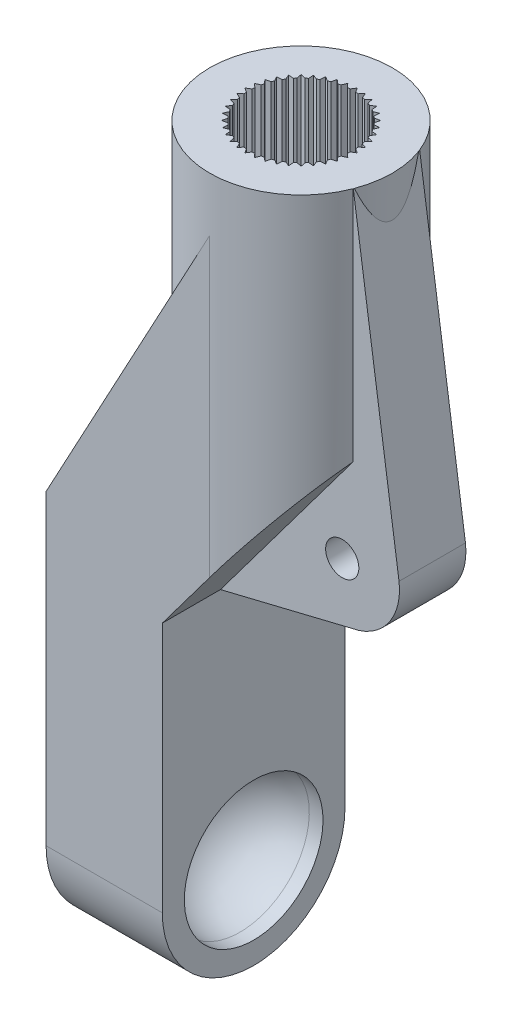
SolidWorks part; units mm, degrees
ref_plane "Front Plane" through (0, 0, 0) normal (0, 0, 1) x (1, 0, 0)
ref_plane "Top Plane" through (0, 0, 0) normal (0, 1, 0) x (1, 0, 0)
ref_plane "Right Plane" through (0, 0, 0) normal (1, 0, 0) x (0, 0, -1)
sketch "Sketch1" plane through (0, 0, 0) normal (0, 0, 1) x (1, 0, 0)
  line L0 (-0.147, 37.772) -> (-0.147, 24.3244)
  line L5 (2.4991, 12.8811) -> (10.853, 24.0251)
  line L6 (-4.501, 16.2484) -> (-0.147, 24.3244)
  line L7 (-0.147, 37.772) -> (10.853, 37.772)
  line L8 (10.853, 24.0251) -> (10.853, 37.772)
  line L9 (2.499, -7.728) -> (-4.501, -7.728)
  line L10 (10.853, 37.772) -> (13.4659, 16.992)
  line L11 (11.4819, 14.7528) -> (3.9024, 14.7528)
  line L12 (-4.501, -3.0008) -> (-4.501, 10.9802) construction
  line L14 (-7.001, 11.6112) -> (-0.147, 24.3244) construction
  line L15 (2.499, -8.0008) -> (2.4991, 8.7131) construction
  line L17 (-0.001, -5.5008) -> (-7.001, -5.5008) construction
  line L18 (-0.0009, 9.5461) -> (10.853, 24.0251) construction
  line L19 (-0.001, -5.5008) -> (-0.0009, 9.5461) construction
  line L35 (-4.501, -7.728) -> (-4.501, 16.2484)
  line L36 (2.499, -7.728) -> (2.4991, 12.8811)
  line L39 (2.499, -8.0008) -> (-9.501, -8.0008) construction
  line L40 (-9.501, -8.0008) -> (-9.501, 12.2422) construction
  line L41 (-9.501, 12.2422) -> (-2.647, 24.9553) construction
  line L42 (-2.647, 40.272) -> (-2.647, 24.9553) construction
  line L43 (-2.647, 40.272) -> (13.353, 40.272) construction
  line L44 (13.353, 23.1921) -> (13.353, 40.272) construction
  line L45 (2.4991, 8.7131) -> (13.353, 23.1921) construction
  line L47 (-2.501, -3.0008) -> (-4.501, -3.0008) construction
  line L48 (-2.501, -3.0008) -> (-2.5009, 10.3791) construction
  line L49 (-4.501, 10.9802) -> (2.353, 23.6934) construction
  line L50 (-2.5009, 10.3791) -> (8.353, 24.8581) construction
  line L51 (2.353, 35.272) -> (2.353, 23.6934) construction
  line L52 (2.353, 35.272) -> (8.353, 35.272) construction
  line L53 (8.353, 24.8581) -> (8.353, 35.272) construction
  line L54 (-7.001, -5.5008) -> (-7.001, 11.6112) construction
  circle A1 centre (9.8324, 18.1659) radius 1
  arc A2 (11.4819, 14.7528) -> (13.4659, 16.992) centre (11.4803, 16.7528) ccw
  point P2 (5.353, -2.228)
  point P4 (-7.6871, -2.228)
  point P20 (-7.001, -7.5008)
  point P21 (-7.001, 15.8257)
  dimension "D1" = 11
  dimension "D2" = 2.5
  dimension "D3" = 20.78
  dimension "D6" = 2.5
extrude "Boss-Extrude4" add sketch "Sketch1" along normal blind 11 contours L5 L8 L7 L0 L6 region at (2.1882, 17.5356, 0)
fillet "Fillet3" radius 5.5 2 edges at (-1.001, -7.728, 0) (-1.001, -7.728, 11)
sketch "Sketch4" plane through (0, 37.772, 0) normal (0, 1, 0) x (1, 0, 0)
  line L0 (-0.147, -5.5) -> (10.853, -5.5) construction
  line L1 (-0.147, -11) -> (-0.147, 0) construction
  line L2 (10.853, -11) -> (10.853, 0) construction
  line L3 (-0.147, 0) -> (-0.147, -11)
  line L4 (-0.147, -11) -> (10.853, -11)
  line L5 (10.853, -11) -> (10.853, 0)
  line L6 (10.853, 0) -> (-0.147, 0)
  circle A0 centre (5.353, -5.5) radius 5.5
  line M2 (-0.147, 0) -> (-0.147, -11)
  line M3 (-0.147, -11) -> (10.853, -11)
extrude "Cut-Extrude3" cut sketch "Sketch4" against normal up to surface (13.4477 mm away) contours A0 L6 M2 | A0 L3 M3 region at (1.0815, 37.772, 1.2285) region at (1.0815, 37.772, 9.7715) up to face at (-2.324, 20.2864, 5.5)
sketch "Sketch7" plane through (0, 37.772, 0) normal (0, 1, 0) x (1, 0, 0)
  line L0 (10.853, 0) -> (10.853, -11)
  line L1 (10.853, -11) -> (5.353, -11)
  line L2 (5.353, 0) -> (10.853, 0)
  circle A0 centre (5.353, -5.5) radius 5.5
  line M2 (5.353, -11) -> (10.853, -11)
  line M3 (10.853, -11) -> (10.853, 0)
  line M4 (10.853, 0) -> (5.353, 0)
extrude "Cut-Extrude9" cut sketch "Sketch7" against normal through all contours A0 L0 M4 | A0 M2 M3 region at (9.6244, 37.772, 1.2285) region at (9.6244, 37.772, 9.7715)
sketch3d "3DSketch1" plane through (0, 0, 0) normal (0, 0, 1) x (1, 0, 0)
ref_plane "Plane4" through (0, 0, 5.5) normal (0, 0, -1) x (-1, 0, 0)
sketch "Sketch8" plane through (0, 37.772, 0) normal (0, 1, 0) x (1, 0, 0)
  line L0 (5.353, -5.5) -> (10.853, -5.5) construction
  line L1 (8.7409, -5.5) -> (8.4736, -5.3352)
  line L2 (8.7409, -5.5) -> (8.4736, -5.6648)
  line L3 (8.6991, -6.03) -> (8.461, -5.8254)
  line L4 (8.6991, -6.03) -> (8.4094, -6.151)
  line L5 (8.575, -6.5469) -> (8.3718, -6.3076)
  line L6 (8.575, -6.5469) -> (8.2699, -6.6211)
  line L7 (8.3716, -7.0381) -> (8.2083, -6.7699)
  line L8 (8.3716, -7.0381) -> (8.0586, -7.0636)
  line L9 (8.0938, -7.4914) -> (7.9745, -7.2009)
  line L10 (8.0938, -7.4914) -> (7.7807, -7.4676)
  line L11 (7.7486, -7.8956) -> (7.6761, -7.5901)
  line L12 (7.7486, -7.8956) -> (7.443, -7.8232)
  line L13 (7.3443, -8.2409) -> (7.3206, -7.9278)
  line L14 (7.3443, -8.2409) -> (7.0539, -8.1216)
  line L15 (6.891, -8.5186) -> (6.9166, -8.2057)
  line L16 (6.891, -8.5186) -> (6.6228, -8.3554)
  line L17 (6.3999, -8.7221) -> (6.4741, -8.417)
  line L18 (6.3999, -8.7221) -> (6.1605, -8.5189)
  line L19 (5.8829, -8.8462) -> (6.0039, -8.5564)
  line L20 (5.8829, -8.8462) -> (5.6783, -8.608)
  line L21 (5.353, -8.8879) -> (5.5178, -8.6206)
  line L22 (5.353, -8.8879) -> (5.1881, -8.6206)
  line L23 (4.823, -8.8462) -> (5.0276, -8.608)
  line L24 (4.823, -8.8462) -> (4.702, -8.5564)
  line L25 (4.306, -8.7221) -> (4.5454, -8.5189)
  line L26 (4.306, -8.7221) -> (4.2318, -8.417)
  line L27 (3.8149, -8.5186) -> (4.0831, -8.3554)
  line L28 (3.8149, -8.5186) -> (3.7893, -8.2057)
  line L29 (3.3616, -8.2409) -> (3.652, -8.1216)
  line L30 (3.3616, -8.2409) -> (3.3853, -7.9278)
  line L31 (2.9573, -7.8956) -> (3.2629, -7.8232)
  line L32 (2.9573, -7.8956) -> (3.0298, -7.5901)
  line L33 (2.6121, -7.4914) -> (2.9252, -7.4676)
  line L34 (2.6121, -7.4914) -> (2.7314, -7.2009)
  line L35 (2.3343, -7.0381) -> (2.6473, -7.0636)
  line L36 (2.3343, -7.0381) -> (2.4976, -6.7699)
  line L37 (2.1309, -6.5469) -> (2.436, -6.6211)
  line L38 (2.1309, -6.5469) -> (2.3341, -6.3076)
  line L39 (2.0068, -6.03) -> (2.2965, -6.151)
  line L40 (2.0068, -6.03) -> (2.2449, -5.8254)
  line L41 (1.965, -5.5) -> (2.2323, -5.6648)
  line L42 (1.965, -5.5) -> (2.2323, -5.3352)
  line L43 (2.0068, -4.97) -> (2.2449, -5.1746)
  line L44 (2.0068, -4.97) -> (2.2965, -4.849)
  line L45 (2.1309, -4.4531) -> (2.3341, -4.6924)
  line L46 (2.1309, -4.4531) -> (2.436, -4.3789)
  line L47 (2.3343, -3.9619) -> (2.4976, -4.2301)
  line L48 (2.3343, -3.9619) -> (2.6473, -3.9364)
  line L49 (2.6121, -3.5086) -> (2.7314, -3.7991)
  line L50 (2.6121, -3.5086) -> (2.9252, -3.5324)
  line L51 (2.9573, -3.1044) -> (3.0298, -3.4099)
  line L52 (2.9573, -3.1044) -> (3.2629, -3.1768)
  line L53 (3.3616, -2.7591) -> (3.3853, -3.0722)
  line L54 (3.3616, -2.7591) -> (3.652, -2.8784)
  line L55 (3.8149, -2.4814) -> (3.7893, -2.7943)
  line L56 (3.8149, -2.4814) -> (4.0831, -2.6446)
  line L57 (4.306, -2.2779) -> (4.2318, -2.583)
  line L58 (4.306, -2.2779) -> (4.5454, -2.4811)
  line L59 (4.823, -2.1538) -> (4.702, -2.4436)
  line L60 (4.823, -2.1538) -> (5.0276, -2.392)
  line L61 (5.353, -2.1121) -> (5.1881, -2.3794)
  line L62 (5.353, -2.1121) -> (5.5178, -2.3794)
  line L63 (5.8829, -2.1538) -> (5.6783, -2.392)
  line L64 (5.8829, -2.1538) -> (6.0039, -2.4436)
  line L65 (6.3999, -2.2779) -> (6.1605, -2.4811)
  line L66 (6.3999, -2.2779) -> (6.4741, -2.583)
  line L67 (6.891, -2.4814) -> (6.6228, -2.6446)
  line L68 (6.891, -2.4814) -> (6.9166, -2.7943)
  line L69 (7.3443, -2.7591) -> (7.0539, -2.8784)
  line L70 (7.3443, -2.7591) -> (7.3206, -3.0722)
  line L71 (7.7486, -3.1044) -> (7.443, -3.1768)
  line L72 (7.7486, -3.1044) -> (7.6761, -3.4099)
  line L73 (8.0938, -3.5086) -> (7.7807, -3.5324)
  line L74 (8.0938, -3.5086) -> (7.9745, -3.7991)
  line L75 (8.3716, -3.9619) -> (8.0586, -3.9364)
  line L76 (8.3716, -3.9619) -> (8.2083, -4.2301)
  line L77 (8.575, -4.4531) -> (8.2699, -4.3789)
  line L78 (8.575, -4.4531) -> (8.3718, -4.6924)
  line L79 (8.6991, -4.97) -> (8.4161, -4.8815)
  line L80 (8.6991, -4.97) -> (8.461, -5.1746)
  line L81 (8.6991, -4.97) -> (8.4094, -4.849) [skipped]
  arc A0 (7.7807, -3.5324) -> (7.6761, -3.4099) centre (5.353, -5.5) ccw
  circle A1 centre (5.353, -5.5) radius 5.5 construction
  arc A2 (8.0586, -3.9364) -> (7.9745, -3.7991) centre (5.353, -5.5) ccw
  arc A3 (8.2699, -4.3789) -> (8.2083, -4.2301) centre (5.353, -5.5) ccw
  arc A4 (8.4736, -5.3352) -> (8.461, -5.1746) centre (5.353, -5.5) ccw
  arc A5 (8.461, -5.8254) -> (8.4736, -5.6648) centre (5.353, -5.5) ccw
  arc A6 (8.3718, -6.3076) -> (8.4094, -6.151) centre (5.353, -5.5) ccw
  arc A7 (8.2083, -6.7699) -> (8.2699, -6.6211) centre (5.353, -5.5) ccw
  arc A8 (7.9745, -7.2009) -> (8.0586, -7.0636) centre (5.353, -5.5) ccw
  arc A9 (7.6761, -7.5901) -> (7.7807, -7.4676) centre (5.353, -5.5) ccw
  arc A10 (7.3206, -7.9278) -> (7.443, -7.8232) centre (5.353, -5.5) ccw
  arc A11 (6.9166, -8.2057) -> (7.0539, -8.1216) centre (5.353, -5.5) ccw
  arc A12 (6.4741, -8.417) -> (6.6228, -8.3554) centre (5.353, -5.5) ccw
  arc A13 (6.0039, -8.5564) -> (6.1605, -8.5189) centre (5.353, -5.5) ccw
  arc A14 (5.5178, -8.6206) -> (5.6783, -8.608) centre (5.353, -5.5) ccw
  arc A15 (5.0276, -8.608) -> (5.1881, -8.6206) centre (5.353, -5.5) ccw
  arc A16 (4.5454, -8.5189) -> (4.702, -8.5564) centre (5.353, -5.5) ccw
  arc A17 (4.0831, -8.3554) -> (4.2318, -8.417) centre (5.353, -5.5) ccw
  arc A18 (3.652, -8.1216) -> (3.7893, -8.2057) centre (5.353, -5.5) ccw
  arc A19 (3.2629, -7.8232) -> (3.3853, -7.9278) centre (5.353, -5.5) ccw
  arc A20 (2.9252, -7.4676) -> (3.0298, -7.5901) centre (5.353, -5.5) ccw
  arc A21 (2.6473, -7.0636) -> (2.7314, -7.2009) centre (5.353, -5.5) ccw
  arc A22 (2.436, -6.6211) -> (2.4976, -6.7699) centre (5.353, -5.5) ccw
  arc A23 (2.2965, -6.151) -> (2.3341, -6.3076) centre (5.353, -5.5) ccw
  arc A24 (2.2323, -5.6648) -> (2.2449, -5.8254) centre (5.353, -5.5) ccw
  arc A25 (2.2449, -5.1746) -> (2.2323, -5.3352) centre (5.353, -5.5) ccw
  arc A26 (2.3341, -4.6924) -> (2.2965, -4.849) centre (5.353, -5.5) ccw
  arc A27 (2.4976, -4.2301) -> (2.436, -4.3789) centre (5.353, -5.5) ccw
  arc A28 (2.7314, -3.7991) -> (2.6473, -3.9364) centre (5.353, -5.5) ccw
  arc A29 (3.0298, -3.4099) -> (2.9252, -3.5324) centre (5.353, -5.5) ccw
  arc A30 (3.3853, -3.0722) -> (3.2629, -3.1768) centre (5.353, -5.5) ccw
  arc A31 (3.7893, -2.7943) -> (3.652, -2.8784) centre (5.353, -5.5) ccw
  arc A32 (4.2318, -2.583) -> (4.0831, -2.6446) centre (5.353, -5.5) ccw
  arc A33 (4.702, -2.4436) -> (4.5454, -2.4811) centre (5.353, -5.5) ccw
  arc A34 (5.6783, -2.392) -> (5.5178, -2.3794) centre (5.353, -5.5) ccw
  arc A35 (6.1605, -2.4811) -> (6.0039, -2.4436) centre (5.353, -5.5) ccw
  arc A36 (6.6228, -2.6446) -> (6.4741, -2.583) centre (5.353, -5.5) ccw
  arc A37 (7.0539, -2.8784) -> (6.9166, -2.7943) centre (5.353, -5.5) ccw
  arc A38 (7.443, -3.1768) -> (7.3206, -3.0722) centre (5.353, -5.5) ccw
  arc A39 (8.4161, -4.8815) -> (8.3718, -4.6924) centre (5.353, -5.5) ccw
  arc A40 (5.1881, -2.3794) -> (5.0276, -2.392) centre (5.353, -5.5) ccw
  dimension "D1" = 6.25
  dimension "D2" = 40
sketch "Sketch13" plane through (0, 0, 5.5) normal (0, 0, -1) x (-1, 0, 0)
  line L2 (-2.4991, 12.8811) -> (-10.853, 14.9214)
  line L3 (-5.353, 37.772) -> (-2.4991, 12.8811)
  line L5 (-10.5002, 37.772) -> (-13.2525, 18.6895)
  line L9 (-10.5002, 37.772) -> (-5.353, 37.772)
  circle A2 centre (-9.8324, 18.1659) radius 1
  arc A3 (-13.2525, 18.6895) -> (-10.853, 14.9214) centre (-9.7798, 18.2528) ccw
  dimension "D1" = 3.5
extrude "Boss-Extrude8" add sketch "Sketch13" along normal mid plane 4
extrude "Cut-Extrude13" cut sketch "Sketch8" against normal blind 13
sketch "Sketch16" plane through (2.499, 0, 0) normal (1, 0, 0) x (0, 0, -1)
  circle A0 centre (-5.5, -2.228) radius 4.175
  dimension "D1" = 8.35
  dimension "D2" = 5.5
extrude "Cut-Extrude14" cut sketch "Sketch16" against normal blind 5
fillet "Fillet5" radius 4.175 1 edges at (-2.501, 1.947, 5.5)
